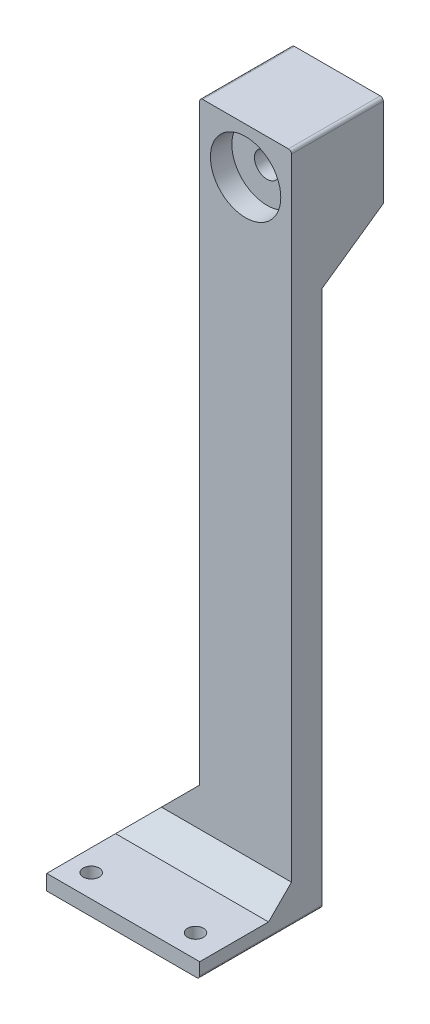
SolidWorks part; units mm, degrees
ref_plane "Front Plane" through (0, 0, 0) normal (0, 0, 1) x (1, 0, 0)
ref_plane "Top Plane" through (0, 0, 0) normal (0, 1, 0) x (1, 0, 0)
ref_plane "Right Plane" through (0, 0, 0) normal (1, 0, 0) x (0, 0, -1)
sketch "Sketch1" plane through (0, 0, 0) normal (0, 0, 1) x (1, 0, 0)
  line L0 (0, 0) -> (537.434, 195.61) construction
  line L1 (537.434, 195.61) -> (537.434, 0)
  line L3 (527.1734, 223.8008) -> (-10.2606, 28.1908) construction
  line L4 (-10.2606, 28.1908) -> (0, 0) construction
  line L5 (532.3037, 209.7054) -> (518.2083, 204.5751) construction
  line L9 (507.434, 184.6909) -> (507.434, 0)
  line L10 (507.434, 0) -> (537.434, 0)
  line L11 (518.2083, 204.5751) -> (551.7163, 204.5751) construction
  line L12 (522.434, 0) -> (522.434, 204.5751) construction
  line L13 (522.434, 204.5751) -> (522.434, 219.5751) construction
  line L14 (537.434, 195.61) -> (537.434, 219.5751)
  line L15 (537.434, 219.5751) -> (507.434, 219.5751)
  line L16 (507.434, 219.5751) -> (507.434, 184.6909)
  circle A0 centre (522.434, 204.5751) radius 4.1
extrude "Boss-Extrude1" add sketch "Sketch1" along normal blind 10
sketch "Sketch2" plane through (0, 0, 10) normal (0, 0, 1) x (1, 0, 0)
  line L0 (537.434, 0) -> (537.434, 219.5751) construction
  line L1 (507.434, 0) -> (537.434, 0)
  line L3 (507.434, 5) -> (537.434, 5)
  line L4 (537.434, 0) -> (537.434, 5)
  line L5 (507.434, 0) -> (487.434, 0)
  line L6 (487.434, 0) -> (487.434, 5)
  line L7 (487.434, 5) -> (507.434, 5)
extrude "Boss-Extrude2" add sketch "Sketch2" along normal blind 30 and the other way blind 10
sketch "Sketch4" plane through (0, 5, 0) normal (0, 1, 0) x (1, 0, 0)
  line L0 (521.5294, -25) -> (537.434, -25) construction
  line L1 (537.434, -32.5) -> (528.5748, -32.5) construction
  line L2 (537.434, -25) -> (537.434, -40) construction
  line L3 (507.434, -25) -> (521.5294, -25) construction
  line L4 (487.434, -32.5) -> (494.484, -32.5) construction
  line L5 (487.434, 0) -> (487.434, -40) construction
  circle A2 centre (528.5748, -32.5) radius 2.6
  circle A3 centre (494.484, -32.5) radius 2.6
extrude "Cut-Extrude1" cut sketch "Sketch4" against normal blind 20
ref_plane "Plane1" through (0, 5, 0) normal (0, 1, 0) x (1, 0, 0)
chamfer "Chamfer1" distance 20 angle 45 1 edges at (507.434, 5, 5)
chamfer "Chamfer2" distance 7.5 angle 45 1 edges at (512.434, 5, 10)
sketch "Sketch7" plane through (0, 0, 10) normal (0, 0, 1) x (1, 0, 0)
  circle A0 centre (522.434, 204.5751) radius 11.5
extrude "Cut-Extrude2" cut sketch "Sketch7" against normal blind 7
sketch "Sketch9" plane through (0, 0, 0) normal (0, 0, -1) x (-1, 0, 0)
  line L0 (-507.434, 219.5751) -> (-507.434, 25) construction
  line L1 (-537.434, 219.5751) -> (-507.434, 219.5751)
  line L2 (-537.434, 219.5751) -> (-537.434, 189.5751)
  line L3 (-537.434, 189.5751) -> (-507.434, 189.5751)
  line L4 (-507.434, 219.5751) -> (-507.434, 189.5751)
  circle A0 centre (-522.434, 204.5751) radius 4.1
extrude "Boss-Extrude4" add sketch "Sketch9" along normal blind 13
sketch "Sketch8" plane through (0, 0, -13) normal (0, 0, -1) x (-1, 0, 0)
  line L0 (-507.434, 189.5751) -> (-507.434, 25) construction
  line L1 (-537.434, 219.5751) -> (-507.434, 219.5751)
  line L2 (-537.434, 219.5751) -> (-537.434, 189.5751)
  line L3 (-537.434, 189.5751) -> (-507.434, 189.5751)
  line L4 (-507.434, 219.5751) -> (-507.434, 189.5751)
  circle A0 centre (-522.434, 204.5751) radius 11.4
  point P10 (0, 0)
extrude "Boss-Extrude3" add sketch "Sketch8" along normal blind 7
chamfer "Chamfer3" distance 20 angle 35 1 edges at (522.434, 189.5751, 0) first distance on face at (522.434, 189.5751, -10)
fillet "Fillet2" radius 1 3 edges at (537.434, 0, 20) (537.434, 219.5751, -5) (507.434, 219.5751, -5)
